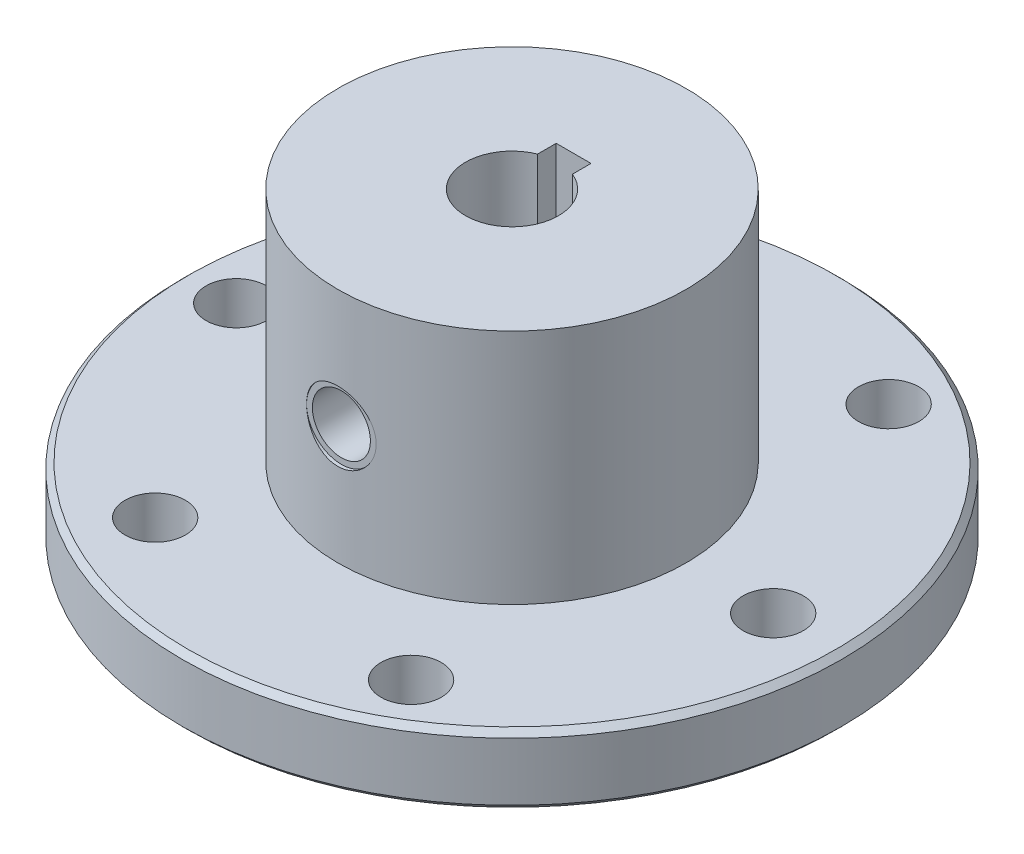
SolidWorks part; units mm, degrees
ref_plane "前视基准面" through (0, 0, 0) normal (0, 0, 1) x (1, 0, 0)
ref_plane "上视基准面" through (0, 0, 0) normal (0, 1, 0) x (1, 0, 0)
ref_plane "右视基准面" through (0, 0, 0) normal (1, 0, 0) x (0, 0, -1)
other "Configuration Table"
sketch "草图1" plane through (0, 0, 0) normal (0, 1, 0) x (1, 0, 0)
  circle A0 centre (0, 0) radius 28.4
  dimension "D1" = 56.8
extrude "凸台-拉伸1" add sketch "草图1" along normal blind 6
sketch "草图2" plane through (0, 0, 0) normal (0, 1, 0) x (1, 0, 0)
  circle A0 centre (0, 0) radius 15
  dimension "D1" = 30
extrude "凸台-拉伸2" add sketch "草图2" along normal blind 20.4 from surface starting at face at (0, 6, 28.4)
sketch "草图3" plane through (0, 0, 0) normal (0, 1, 0) x (1, 0, 0)
  circle A0 centre (0, 0) radius 4
  dimension "D1" = 8
extrude "切除-拉伸1" cut sketch "草图3" along normal up to surface (26.4 mm away) from surface up to face at (0, 26.4, 15) starting at face at (0, 0, 28.4)
sketch "草图4" plane through (0, 0, 0) normal (0, 1, 0) x (1, 0, 0)
  line L0 (-1000, 0) -> (49000, 0) construction
  line L1 (0, -1000) -> (0, 49000) construction
  line L2 (0, 0) -> (25000, 43301.2702) construction
  line L3 (0, 0) -> (-25000, 43301.2702) construction
  circle A0 centre (0, 0) radius 23.75 construction
  circle A7 centre (0, 0) radius 22.5 construction
  circle A8 centre (11.875, 20.5681) radius 2.6
  circle A9 centre (22.5, 0) radius 2.6
  circle A10 centre (11.875, -20.5681) radius 2.6
  circle A11 centre (-11.25, -19.4856) radius 2.6
  circle A12 centre (-23.75, 0) radius 2.6
  circle A13 centre (-11.25, 19.4856) radius 2.6
  dimension "D3" = 47.5
  dimension "D4" = 45
  dimension "D5" = 5.2
  dimension "D6" = 5.2
  dimension "D7" = 5.2
  dimension "D8" = 5.2
  dimension "D9" = 5.2
  dimension "D10" = 5.2
  dimension "D1" = 30
  dimension "D2" = 30
extrude "切除-拉伸3" cut sketch "草图4" against normal up to surface from surface up to face at (0, 0, 4) starting at face at (0, 6, 15)
sketch "草图5" plane through (0, 0, 0) normal (0, 1, 0) x (1, 0, 0)
  line L0 (0, -1000) -> (0, 49000) construction
  line L1 (-1.5, 3.7081) -> (1.5, 3.7081)
  line L2 (1.5, 3.7081) -> (1.5, 5.3081)
  line L3 (1.5, 5.3081) -> (-1.5, 5.3081)
  line L4 (-1.5, 5.3081) -> (-1.5, 3.7081)
  circle A0 centre (0, 0) radius 4 construction
  circle A1 centre (0, 0) radius 4 construction
  point P8 (0, 3.7081)
  dimension "D1" = 3
  dimension "D2" = 1.6
extrude "切除-拉伸4" cut sketch "草图5" against normal up to surface from surface up to face at (-11.25, 0, -16.8856) starting at face at (0, 26.4, 4)
sketch "草图8" plane through (0, 0, 0) normal (0, 1, 0) x (1, 0, 0)
  line L0 (0, -1000) -> (0, 49000) construction
  line L1 (-3, -14.6969) -> (3, -14.6969)
  arc A0 (-3, -14.6969) -> (3, -14.6969) centre (0, 0) ccw
  point P8 (0, -14.6969)
  dimension "D1" = 30
  dimension "D2" = 6
extrude "切除-拉伸5" cut sketch "草图8" against normal up to surface (-6 mm away) from surface up to face at (-11.25, 6, -16.8856) starting at face at (0, 26.4, 15)
sketch "草图6" plane through (0, 0, 0) normal (0, 0, 1) x (1, 0, 0)
  line L0 (15, 26.4) -> (-15, 6) construction
  line L1 (-15, 26.4) -> (15, 26.4) construction
  line L2 (-15, 26.4) -> (-15, 6) construction
  line L3 (-15, 6) -> (15, 6) construction
  line L4 (15, 26.4) -> (15, 6) construction
  line L5 (-15, 26.4) -> (15, 6) construction
  line L7 (-3, 6) -> (3, 6)
  line L8 (-3, 6) -> (-3, 26.4)
  line L9 (-3, 26.4) -> (3, 26.4)
  line L10 (3, 6) -> (3, 26.4)
  line L11 (-3, 6) -> (3, 26.4) construction
  line L12 (-3, 26.4) -> (3, 6) construction
  circle A0 centre (0, 16.2) radius 3
  point P6 (0, 16.2)
  point P7 (0, 16.2)
  dimension "D1" = 6
extrude "凸台-拉伸4" add sketch "草图6" along normal up to surface from surface contours A0 L10 L9 L8 | A0 L8 L7 L10 region at (0, 9.9505, 0) region at (0, 22.4495, 0) up to face at (0, 16.2, -0.1515) starting at face at (0, 16.2, 14.6969)
sketch "草图9" plane through (0, 0, 0) normal (0, 0, 1) x (1, 0, 0)
  point P0 (0, 16.2)
hole_wizard "M6 螺纹孔1" positions "草图10" profile "草图11" tap size "M6" standard "ISO"
sketch "草图10" plane through (0, 0, 14.6969) normal (0, 0, 1) x (1, 0, 0)
  point P0 (0, 16.2)
sketch "草图11" plane through (0, 16.2, 14.6969) normal (1, 0, 0) x (0, -1, 0)
  line L0 (0, 0) -> (0, 16.5022)
  line L1 (0, 16.5022) -> (2.5, 15)
  line L2 (2.5, 15) -> (2.5, 0)
  line L5 (2.5, 0) -> (0, 0)
  line L10 (0, 16.5022) -> (-2.5, 15) construction
  line L11 (0, -6.35) -> (0, 107.95) construction
  dimension "螺纹孔钻头直径" = 5
  dimension "螺纹孔钻头深度" = 15
  dimension "导头角度" = 118
cosmetic thread "孔螺蚊线1" parameters "D1"=12, "D2"=6
chamfer "倒角1" distance 0.5 angle 45 2 edges at (0, 6, 28.4) (0, 0, 28.4)
